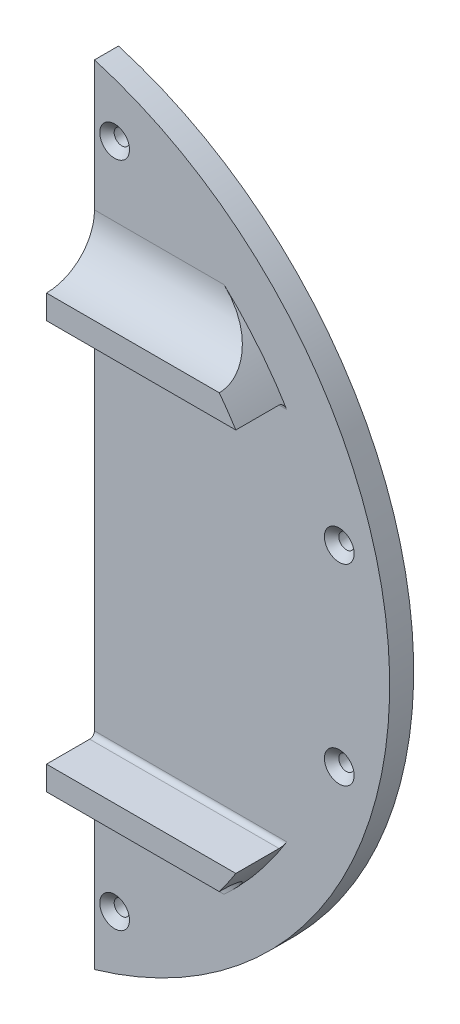
SolidWorks part; units mm, degrees
ref_plane "Front Plane" through (0, 0, 0) normal (1, 0, 0) x (0, 1, 0)
ref_plane "Top Plane" through (0, 0, 0) normal (0, 0, 1) x (0, 1, 0)
ref_plane "Right Plane" through (0, 0, 0) normal (0, 1, 0) x (-1, 0, 0)
sketch "Sketch1" plane through (0, 0, 0) normal (0, 0, 1) x (0, 1, 0)
  line L0 (0, 0) -> (0, -81.5088) construction
  line L5 (-82.0625, -24) -> (82.0625, -24)
  arc A0 (-82.0625, -24) -> (82.0625, -24) centre (0, 0) ccw
  circle A1 centre (-20, -75) radius 1.6
  circle A2 centre (20, -75) radius 1.6
  circle A3 centre (-69.5, -28.2) radius 1.6
  circle A4 centre (69.5, -28.2) radius 1.6
  dimension "D1" = 171
  dimension "D3" = 3.2
  dimension "D7" = 3.2
  dimension "D2" = 75
  dimension "D4" = 20
  dimension "D5" = 69.5
  dimension "D6" = 28.2
  dimension "D8" = 24
extrude "Boss-Extrude2" add sketch "Sketch1" along normal blind 5
sketch "Sketch2" plane through (0, 0, 5) normal (0, 0, 1) x (1, 0, 0)
  line L0 (24, 82.0625) -> (24, -82.0625) construction
  line L1 (60, 45) -> (24, 45)
  line L3 (63.4429, 40) -> (24, 40)
  line L4 (24, 45) -> (24, 40)
  line L6 (24, -45) -> (24, -40)
  line L7 (63.4429, -40) -> (24, -40)
  line L8 (60, -45) -> (24, -45)
  arc A3 (60, -45) -> (63.4429, -40) centre (0, 0) ccw
  arc A4 (63.4429, 40) -> (60, 45) centre (0, 0) ccw
  dimension "D1" = 150
  dimension "D2" = 40
extrude "Boss-Extrude3" add sketch "Sketch2" along normal blind 10
chamfer "Chamfer1" distance 1.5 angle 45 4 edges at (29.8, -69.5, 5) (76.6, -20, 5) (73.4, 20, 5) (26.6, 69.5, 5)
fillet "Fillet1" radius 10 2 edges at (42, -45, 5) (42, 45, 5)
fillet "Fillet2" radius 1 2 edges at (43.7214, -40, 5) (43.7214, 40, 5)
